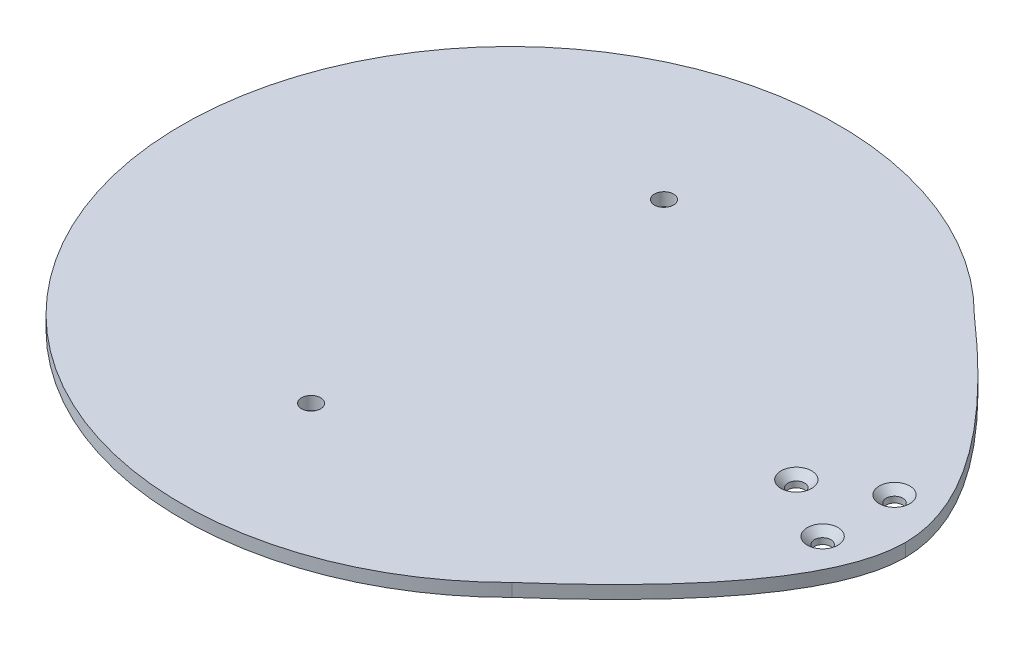
SolidWorks part; units mm, degrees
ref_plane "Ebene vorne" through (0, 0, 0) normal (0, 0, 1) x (1, 0, 0)
ref_plane "Ebene oben" through (0, 0, 0) normal (0, 1, 0) x (1, 0, 0)
ref_plane "Ebene rechts" through (0, 0, 0) normal (1, 0, 0) x (0, 0, -1)
sketch "Skizze1" plane through (0, 0, 0) normal (0, 1, 0) x (1, 0, 0)
  line L0 (28.9708, -44.5268) -> (28.9708, -44.5303)
  line L1 (60.1894, -0.0013) -> (47.1894, -0.0013) construction
  line L2 (47.1894, -0.0013) -> (-20.3106, -0.0013) construction
  arc A0 (28.9708, 44.5276) -> (28.9708, -44.5268) centre (-15.9502, 0.0004) ccw
  circle A1 centre (47.1894, -0.0013) radius 13
  spline S0 degree 2 poles (60.1894, -0.0013) (60.1894, 17.149) (28.9708, 44.5276) knots 0 0 0 1 1 1
  spline S1 degree 2 poles (60.1894, -0.0013) (60.1894, -17.1517) (28.9708, -44.5303) knots 0 0 0 1 1 1
  point P0 (0, 0)
  point P4 (0, 0)
  dimension "D1" = 13
  dimension "D2" = 67.5
extrude "Aufsatz-Linear austragen1" add sketch "Skizze1" along normal blind 2.5 contours S1 A1 S0 A0 L0 | A1 region at (-15.3772, 0, -0.0002) region at (47.1894, 0, 0.0013)
sketch "Skizze2" plane through (0, 2.5, 0) normal (0, 1, 0) x (1, 0, 0)
  line L0 (47.1894, -0.0013) -> (51.1894, 6.9269) construction
  line L1 (60.1894, -0.0013) -> (47.1894, -0.0013) construction
  circle A0 centre (47.1894, -0.0013) radius 3
  circle A1 centre (47.1894, -0.0013) radius 8
  circle A2 centre (51.1894, 6.9269) radius 1.6
  circle A3 centre (51.1894, -6.9296) radius 1.6
  circle A4 centre (39.1894, -0.0013) radius 1.6
  circle A5 centre (47.1894, -0.0013) radius 13
  point P13 (47.1894, -0.0013)
  dimension "D1" = 6
  dimension "D2" = 16
  dimension "D3" = 3.2
  dimension "D5" = 60
  dimension "D4" = 3
extrude "Schnitt-Linear austragen1" cut sketch "Skizze2" against normal through all contours A1 A2 | A2 L0 A1 | L0 A2 A1 | A1 A3 | A1 A3 | A1 A4 | A1 A4 region at (50.2677, 2.5, -6.6425) region at (51.4039, 2.5, -5.9865) region at (51.5141, 2.5, -7.4893) region at (39.8964, 2.5, 0.0013) region at (38.5399, 2.5, 0.0013) region at (51.5141, 2.5, 7.492) region at (50.8358, 2.5, 6.3172)
chamfer "Fase1" distance 1.35 angle 45 3 edges at (51.1894, 2.5, 8.5296) (39.1894, 2.5, 1.6013) (51.1894, 2.5, -5.3269)
sketch "Skizze3" plane through (0, 2.5, 0) normal (0, 1, 0) x (1, 0, 0)
  line L0 (-20.3106, -34.0013) -> (-20.3106, 33.9987)
  circle A0 centre (-20.3106, 33.9987) radius 1.85
  circle A1 centre (-20.3106, -34.0013) radius 1.85
  point P4 (-20.3106, -0.0013)
  dimension "D2" = 3.7
  dimension "D3" = 3.7
  dimension "D1" = 68
extrude "Schnitt-Linear austragen2" cut sketch "Skizze3" against normal through all contours A1 | A0 region at (-21.5818, 2.5, -35.2698) region at (-19.0395, 2.5, 32.7302)
